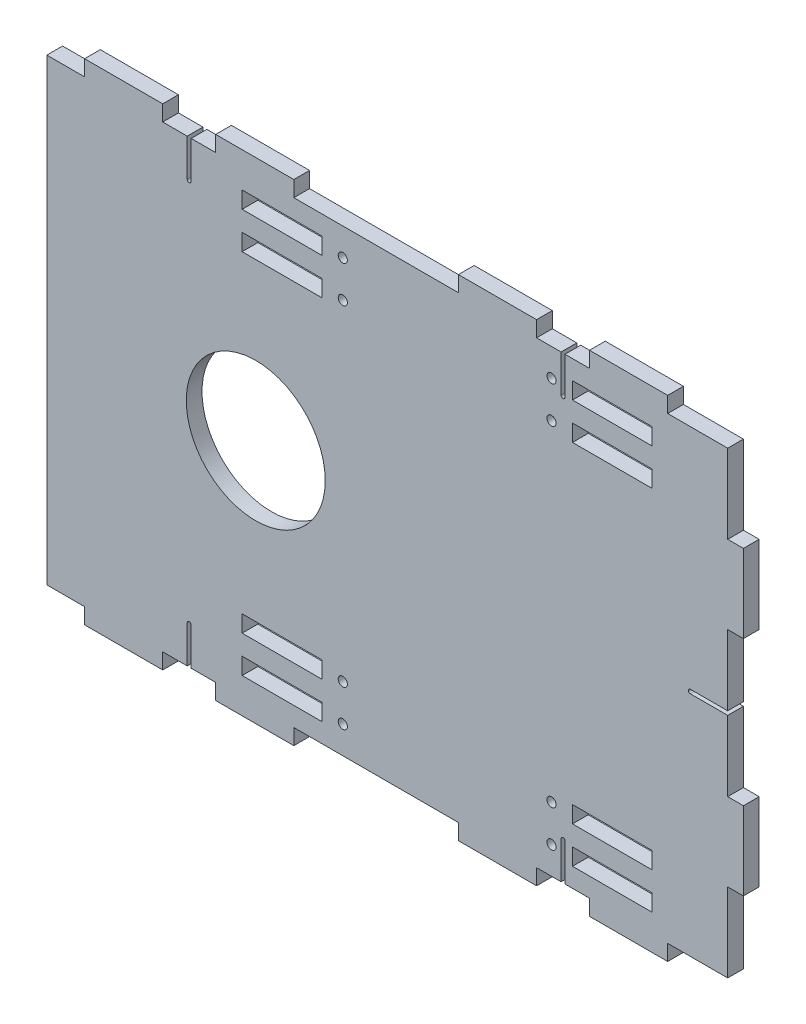
SolidWorks part; units mm, degrees
ref_plane "Plano frontal" through (0, 0, 0) normal (0, 0, 1) x (1, 0, 0)
ref_plane "Plano superior" through (0, 0, 0) normal (0, 1, 0) x (1, 0, 0)
ref_plane "Plano direito" through (0, 0, 0) normal (1, 0, 0) x (0, 0, -1)
sketch "Esboço1" plane through (0, 0, 0) normal (0, 0, 1) x (1, 0, 0)
  line L1 (0, 0) -> (270, 0)
  line L2 (0, 0) -> (0, 187)
  line L3 (0, 187) -> (270, 187)
  line L4 (270, 0) -> (270, 187)
  dimension "D1" = 270
  dimension "D2" = 187
extrude "Ressalto-extrusão1" add sketch "Esboço1" along normal blind 6
sketch "Esboço2" plane through (0, 0, 0) normal (0, 0, -1) x (-1, 0, 0)
  line L1 (-270, 187) -> (0, 187) construction
  line L2 (-271.2, 187) -> (-241.1, 187)
  line L3 (-271.2, 187) -> (-271.2, 181)
  line L4 (-271.2, 181) -> (-241.1, 181)
  line L5 (-241.1, 187) -> (-241.1, 181)
  line L6 (-211.3, 187) -> (-191.1, 187)
  line L7 (-211.3, 187) -> (-211.3, 181)
  line L8 (-211.3, 181) -> (-191.1, 181)
  line L9 (-191.1, 187) -> (-191.1, 181)
  line L10 (0, 187) -> (0, 0) construction
  line L11 (-161.3, 187) -> (-98.5167, 187)
  line L12 (-161.3, 187) -> (-161.3, 181)
  line L13 (-161.3, 181) -> (-98.5167, 181)
  line L14 (-98.5167, 187) -> (-98.5167, 181)
  line L15 (-68.7167, 187) -> (-48.5167, 187)
  line L16 (-68.7167, 187) -> (-68.7167, 181)
  line L17 (-68.7167, 181) -> (-48.5167, 181)
  line L18 (-48.5167, 187) -> (-48.5167, 181)
  line L19 (-18.7167, 187) -> (0, 187)
  line L20 (-18.7167, 187) -> (-18.7167, 181)
  line L21 (-18.7167, 181) -> (0, 181)
  line L22 (0, 187) -> (0, 181)
  line L23 (-270, 187) -> (0, 187) construction
  line L24 (-18.6167, 187) -> (-18.6167, 181) construction
  line L25 (-68.6167, 187) -> (-68.6167, 181) construction
  line L26 (-161.2, 187) -> (-161.2, 181) construction
  line L27 (-209.5975, 187) -> (-206.8218, 187) construction
  line L28 (-211.2, 187) -> (-211.2, 181) construction
  line L29 (0, 93.5) -> (-270, 93.5) construction
  line L30 (-270, 0) -> (-270, 187) construction
  line L31 (0, 0) -> (0, 6)
  line L32 (-18.7167, 6) -> (0, 6)
  line L33 (-18.7167, 0) -> (-18.7167, 6)
  line L34 (-18.7167, 0) -> (0, 0)
  line L35 (-48.5167, 0) -> (-48.5167, 6)
  line L36 (-68.7167, 6) -> (-48.5167, 6)
  line L37 (-68.7167, 0) -> (-68.7167, 6)
  line L38 (-68.7167, 0) -> (-48.5167, 0)
  line L39 (-98.5167, 0) -> (-98.5167, 6)
  line L40 (-161.3, 6) -> (-98.5167, 6)
  line L41 (-161.3, 0) -> (-161.3, 6)
  line L42 (-161.3, 0) -> (-98.5167, 0)
  line L43 (-191.1, 0) -> (-191.1, 6)
  line L44 (-211.3, 6) -> (-191.1, 6)
  line L45 (-211.3, 0) -> (-211.3, 6)
  line L46 (-211.3, 0) -> (-191.1, 0)
  line L47 (-241.1, 0) -> (-241.1, 6)
  line L48 (-271.2, 6) -> (-241.1, 6)
  line L49 (-271.2, 0) -> (-271.2, 6)
  line L50 (-271.2, 0) -> (-241.1, 0)
  dimension "D1" = 29.8
  dimension "D2" = 6
  dimension "D3" = 0.1
  dimension "D4" = 0.1
  dimension "D5" = 29.8
  dimension "D6" = 0.1
  dimension "D7" = 29.8
  dimension "D8" = 29.8
  dimension "D9" = 0.1
extrude "Corte-extrusão1" cut sketch "Esboço2" against normal blind 6
sketch "Esboço3" plane through (0, 0, 6) normal (0, 0, 1) x (1, 0, 0)
  line L0 (264, 181) -> (264, 6) construction
  line L1 (270, 181) -> (264, 181)
  line L2 (270, 181) -> (270, 150.9)
  line L3 (270, 150.9) -> (264, 150.9)
  line L4 (264, 181) -> (264, 150.9)
  line L5 (270, 6) -> (270, 181) construction
  line L6 (264, 121.1) -> (270, 121.1)
  line L7 (264, 121.1) -> (264, 65.9)
  line L8 (264, 65.9) -> (270, 65.9)
  line L9 (270, 121.1) -> (270, 65.9)
  line L10 (264, 151) -> (270, 151) construction
  line L11 (264, 36.1) -> (270, 36.1)
  line L12 (264, 36.1) -> (264, 6)
  line L13 (264, 6) -> (270, 6)
  line L14 (270, 36.1) -> (270, 6)
  line L15 (264, 36) -> (270, 36) construction
  dimension "D1" = 0.1
  dimension "D2" = 29.8
  dimension "D3" = 0.1
  dimension "D4" = 29.8
extrude "Corte-extrusão2" cut sketch "Esboço3" against normal blind 6
sketch "Esboço4" plane through (0, 0, 6) normal (0, 0, 1) x (1, 0, 0)
  line L0 (58.6167, 181) -> (58.6167, 6) construction
  line L1 (68.7167, 181) -> (48.5167, 181) construction
  line L2 (48.5167, 6) -> (68.7167, 6) construction
  line L3 (57.8667, 181) -> (57.8667, 6)
  line L4 (191.1, 6) -> (211.3, 6) construction
  line L5 (201.2, 6) -> (201.2, 181) construction
  line L6 (211.3, 181) -> (191.1, 181) construction
  line L7 (264, 94.25) -> (58.6167, 94.25)
  line L8 (264, 121.1) -> (264, 65.9) construction
  line L9 (264, 93.5) -> (58.6167, 93.5) construction
  line L10 (59.3667, 181) -> (59.3667, 6)
  line L11 (264, 92.75) -> (58.6167, 92.75)
  line L12 (201.95, 6) -> (201.95, 181)
  line L13 (200.45, 6) -> (200.45, 181)
  line L15 (57.8667, 181) -> (59.3667, 181)
  line L16 (57.8667, 181) -> (57.8667, 6)
  line L17 (57.8667, 6) -> (59.3667, 6)
  line L18 (59.3667, 181) -> (59.3667, 6)
  line L19 (57.8667, 166) -> (249, 166)
  line L20 (57.8667, 166) -> (57.8667, 21)
  line L21 (57.8667, 21) -> (249, 21)
  line L22 (249, 166) -> (249, 21)
  line L23 (58.6167, 181) -> (264, 181)
  line L24 (58.6167, 181) -> (58.6167, 6)
  line L25 (58.6167, 6) -> (264, 6)
  line L26 (264, 181) -> (264, 6)
  line M10 (264, 65.9) -> (264, 121.1)
  line M19 (211.3, 181) -> (191.1, 181)
  line M27 (68.7167, 181) -> (48.5167, 181)
  line M37 (48.5167, 6) -> (68.7167, 6)
  line M45 (191.1, 6) -> (211.3, 6)
  dimension "D1" = 0.75
  dimension "D5" = 15
  dimension "D6" = 15
  dimension "D7" = 15
  dimension "D2" = 0.75
  dimension "D3" = 0.75
  dimension "D4" = 0.75
extrude "Corte-extrusão3" cut sketch "Esboço4" against normal blind 6 contours L24 L15 L3 L19 | L24 L19 L10 M27 | L24 L21 L3 M37 | L21 L24 L17 L18 | L21 L13 L12 M45 | L7 L22 L11 M10 | L13 L19 L12 M19 region at (58.2417, 173.5, 6) region at (58.9917, 173.5, 6) region at (58.2417, 13.5, 6) region at (58.9917, 13.5, 6) region at (201.2, 173.5, 6) region at (201.2, 13.5, 6) region at (256.5, 93.5, 6)
sketch "Esboço7" plane through (0, 6, 0) normal (0, 1, 0) x (1, 0, 0)
  line L0 (-1.68, 0) -> (4.32, 0)
  line L2 (18.7167, 0) -> (0, 0) construction
  line L3 (4.32, 0) -> (4.32, -6)
  line L4 (18.7167, -6) -> (0, -6) construction
  line L5 (4.32, -6) -> (0, -6)
  line L6 (0, -6) -> (0, 0)
  dimension "D1" = 6
  dimension "D2" = 1.68
extrude "Corte-extrusão4" cut sketch "Esboço7" along normal blind 194.4 contours L6 L5 L3 L0 region at (2.16, 6, 3)
sketch "Esboço8" plane through (0, 0, 6) normal (0, 0, 1) x (1, 0, 0)
  line L0 (109.2, 23.5) -> (164.8901, 23.5) construction
  line L1 (78.8, 33.7) -> (109.2, 33.7)
  line L2 (78.8, 33.7) -> (78.8, 13.3)
  line L3 (78.8, 13.3) -> (109.2, 13.3)
  line L4 (109.2, 33.7) -> (109.2, 13.3)
  line L5 (78.8, 27.3) -> (109.2, 27.3)
  line L6 (78.8, 27.3) -> (78.8, 19.7)
  line L7 (78.8, 19.7) -> (109.2, 19.7)
  line L8 (109.2, 27.3) -> (109.2, 19.7)
  line L9 (79, 33.5) -> (109, 33.5) construction
  line L10 (79, 33.5) -> (79, 27.5) construction
  line L11 (79, 27.5) -> (109, 27.5) construction
  line L12 (79, 13.5) -> (109, 13.5) construction
  line L13 (79, 19.5) -> (109, 19.5) construction
  line L14 (109, 33.5) -> (109, 27.5) construction
  line L15 (157, 33.5) -> (157, 13.5) construction
  line L17 (204.8, 27.3) -> (204.8, 19.7)
  line L18 (235.2, 19.7) -> (204.8, 19.7)
  line L19 (235.2, 27.3) -> (235.2, 19.7)
  line L20 (235.2, 27.3) -> (204.8, 27.3)
  line L21 (204.8, 33.7) -> (204.8, 13.3)
  line L22 (235.2, 13.3) -> (204.8, 13.3)
  line L23 (235.2, 33.7) -> (235.2, 13.3)
  line L24 (235.2, 33.7) -> (204.8, 33.7)
  line L25 (109.2, 33.7) -> (109.2, 27.3)
  line L26 (109.2, 33.7) -> (109.2, 27.3)
  line L27 (109.2, 30.5) -> (117.2, 30.5) construction
  circle A0 centre (117.2, 30.5) radius 1.75
  circle A1 centre (117.2, 16.5) radius 1.75
  circle A2 centre (196.8, 16.5) radius 1.75
  circle A3 centre (196.8, 30.5) radius 1.75
  dimension "D7" = 3.5
  dimension "D1" = 0.2
  dimension "D2" = 0.2
  dimension "D3" = 0.2
  dimension "D4" = 0.2
  dimension "D5" = 0.2
  dimension "D6" = 0.2
  dimension "D8" = 8
extrude "Corte-extrusão5" cut sketch "Esboço8" against normal blind 25.5 contours L2 L5 L4 L1 | L7 L2 L3 L4 | L23 L18 L21 L22 | L23 L24 L21 L20 | A0 | A1 | A3 | A2 region at (94, 30.5, 6) region at (94, 16.5, 6) region at (220, 30.5, 6) region at (220, 16.5, 6) region at (117.2, 30.5, 6) region at (117.2, 16.5, 6) region at (196.8, 16.5, 6) region at (196.8, 30.5, 6)
ref_plane "Plano1" through (0, 93.5, 0) normal (0, -1, 0) x (-1, 0, 0)
mirror "Espelhar1" about plane through (0, 93.5, 0) normal (0, -1, 0) of "Corte-extrusão5"
sketch "Esboço10" plane through (0, 0, 6) normal (0, 0, 1) x (1, 0, 0)
  line L0 (4.32, 181) -> (4.32, 6) construction
  line L1 (264, 121.1) -> (264, 94.25) construction
  circle A0 centre (84, 93.5) radius 26.5
  point P5 (4.32, 93.5)
  dimension "D1" = 53
  dimension "D2" = 180
extrude "Corte-extrusão6" cut sketch "Esboço10" against normal blind 25.5
fillet "Filete1" radius 0.75 10 edges at (59.3667, 166, 3) (57.8667, 166, 3) (200.45, 166, 3) (201.95, 166, 3) (249, 92.75, 3) (249, 94.25, 3) (201.95, 21, 3) (200.45, 21, 3) (57.8667, 21, 3) (59.3667, 21, 3)
